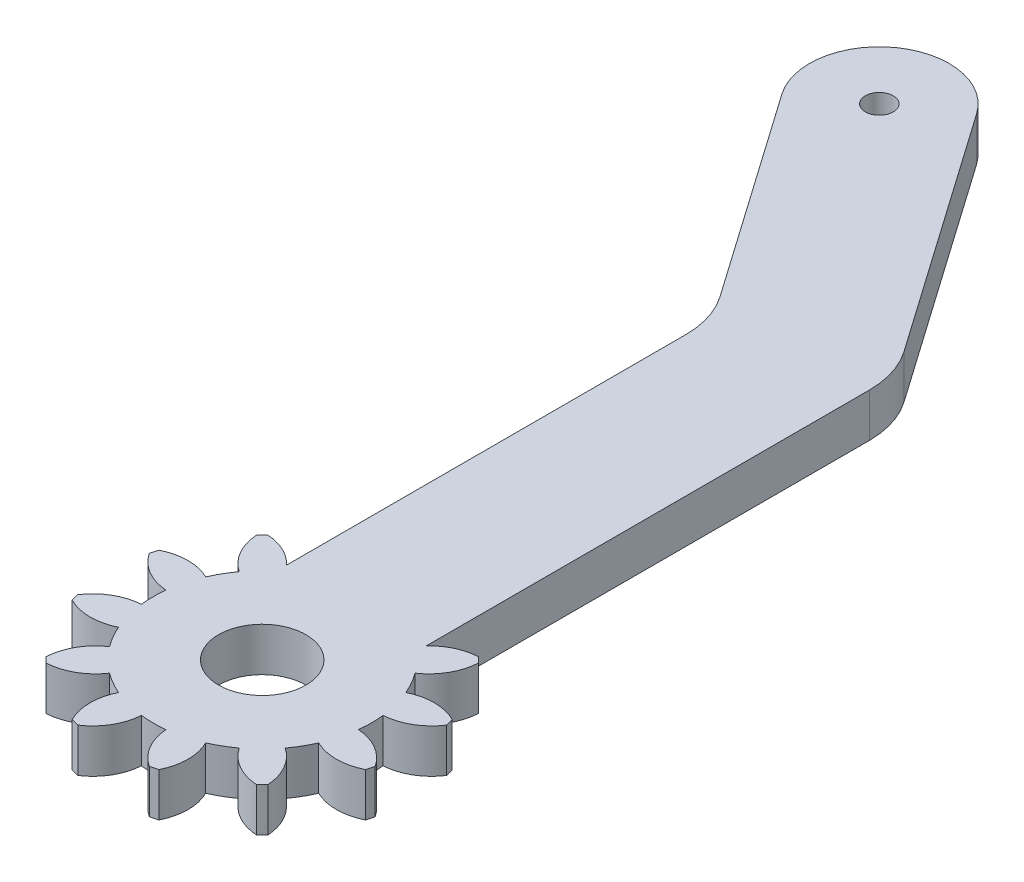
SolidWorks part; units mm, degrees
ref_plane "Front Plane" through (0, 0, 0) normal (0, 0, 1) x (1, 0, 0)
ref_plane "Top Plane" through (0, 0, 0) normal (0, 1, 0) x (1, 0, 0)
ref_plane "Right Plane" through (0, 0, 0) normal (1, 0, 0) x (0, 0, -1)
sketch "Sketch1" plane through (0, 0, 0) normal (0, 1, 0) x (1, 0, 0)
  line L1 (8, 9.6047) -> (8, 64.6702)
  line L2 (8, 96.9801) -> (-8, 96.9801) construction
  line L3 (-8, 96.9801) -> (-8, 59.6254) construction
  line L4 (0, 0) -> (0, 47.5503) construction
  line L5 (-8, 59.6254) -> (-30.9431, 92.3915)
  line L6 (-30.9431, 92.3915) -> (-17.8366, 101.5687)
  line L7 (-17.8366, 101.5687) -> (8, 64.6702)
  line L8 (-8, 59.6254) -> (-8, 9.6047)
  line L9 (8, 64.6702) -> (8, 96.9801) construction
  arc A0 (-8, 9.6047) -> (8, 9.6047) centre (0, 0) ccw
  point P1 (-24.3898, 96.9801)
  dimension "D1" = 25
  dimension "D2" = 16
  dimension "D3" = 100
  dimension "D4" = 16
  dimension "D5" = 145
  dimension "D6" = 40
extrude "Boss-Extrude1" add sketch "Sketch1" along normal blind 5
fillet "Fillet1" 2 edges at (-30.9431, 2.5, -92.3915) (-17.8366, 2.5, -101.5687) type full round first side face at (-19.4715, 2.5, -76.0084) second side face at (-4.9183, 2.5, -83.1194) middle face at (-24.3898, 2.5, -96.9801)
fillet "Fillet2" radius 10 2 edges at (8, 2.5, -64.6702) (-8, 2.5, -59.6254)
sketch "Sketch2" plane through (0, 5, 0) normal (0, 1, 0) x (1, 0, 0)
  circle A0 centre (-19.8012, 90.4269) radius 1.6
  dimension "D1" = 3.2
extrude "Cut-Extrude2" cut sketch "Sketch2" against normal through all contours A0
sketch "Sketch5" plane through (0, 5, 0) normal (0, 1, 0) x (1, 0, 0)
  arc A0 (-12.0517, -12.6888) -> (-7.1035, -9.5148) centre (-12.4017, -6.699) ccw
  arc A1 (-7.1035, -9.5148) -> (-4.6884, -10.9092) centre (0, 0) ccw
  arc A2 (-4.6884, -10.9092) -> (-4.963, -16.7815) centre (0.3993, -14.0897) ccw
  arc A3 (-4.963, -16.7815) -> (-4.0927, -17.0147) centre (0, 0) ccw
  arc A4 (-4.0927, -17.0147) -> (-1.3944, -11.7918) centre (-7.3907, -12.0024) ccw
  arc A5 (-1.3944, -11.7918) -> (1.3944, -11.7918) centre (0, 0) ccw
  arc A6 (1.3944, -11.7918) -> (4.0927, -17.0147) centre (7.3907, -12.0024) ccw
  arc A7 (4.0927, -17.0147) -> (4.963, -16.7815) centre (0, 0) ccw
  arc A8 (4.963, -16.7815) -> (4.6884, -10.9092) centre (-0.3993, -14.0897) ccw
  arc A9 (4.6884, -10.9092) -> (7.1035, -9.5148) centre (0, 0) ccw
  arc A10 (7.1035, -9.5148) -> (12.0517, -12.6888) centre (12.4017, -6.699) ccw
  arc A11 (12.0517, -12.6888) -> (12.6888, -12.0517) centre (0, 0) ccw
  arc A12 (12.6888, -12.0517) -> (9.5148, -7.1035) centre (6.699, -12.4017) ccw
  arc A13 (9.5148, -7.1035) -> (10.9092, -4.6884) centre (0, 0) ccw
  arc A14 (10.9092, -4.6884) -> (16.7815, -4.963) centre (14.0897, 0.3993) ccw
  arc A15 (16.7815, -4.963) -> (17.0147, -4.0927) centre (0, 0) ccw
  arc A16 (17.0147, -4.0927) -> (11.7918, -1.3944) centre (12.0024, -7.3907) ccw
  arc A17 (11.7918, -1.3944) -> (11.7918, 1.3944) centre (0, 0) ccw
  arc A18 (11.7918, 1.3944) -> (17.0147, 4.0927) centre (12.0024, 7.3907) ccw
  arc A19 (17.0147, 4.0927) -> (16.7815, 4.963) centre (0, 0) ccw
  arc A20 (16.7815, 4.963) -> (10.9092, 4.6884) centre (14.0897, -0.3993) ccw
  arc A21 (10.9092, 4.6884) -> (9.5148, 7.1035) centre (0, 0) ccw
  arc A22 (9.5148, 7.1035) -> (12.6888, 12.0517) centre (6.699, 12.4017) ccw
  arc A23 (12.6888, 12.0517) -> (12.0517, 12.6888) centre (0, 0) ccw
  arc A24 (12.0517, 12.6888) -> (7.1035, 9.5148) centre (12.4017, 6.699) ccw
  arc A25 (7.1035, 9.5148) -> (4.6884, 10.9092) centre (0, 0) ccw
  arc A26 (4.6884, 10.9092) -> (4.963, 16.7815) centre (-0.3993, 14.0897) ccw
  arc A27 (4.963, 16.7815) -> (4.0927, 17.0147) centre (0, 0) ccw
  arc A28 (4.0927, 17.0147) -> (1.3944, 11.7918) centre (7.3907, 12.0024) ccw
  arc A29 (1.3944, 11.7918) -> (-1.3944, 11.7918) centre (0, 0) ccw
  arc A30 (-1.3944, 11.7918) -> (-4.0927, 17.0147) centre (-7.3907, 12.0024) ccw
  arc A31 (-4.0927, 17.0147) -> (-4.963, 16.7815) centre (0, 0) ccw
  arc A32 (-4.963, 16.7815) -> (-4.6884, 10.9092) centre (0.3993, 14.0897) ccw
  arc A33 (-4.6884, 10.9092) -> (-7.1035, 9.5148) centre (0, 0) ccw
  arc A34 (-7.1035, 9.5148) -> (-12.0517, 12.6888) centre (-12.4017, 6.699) ccw
  arc A35 (-12.0517, 12.6888) -> (-12.6888, 12.0517) centre (0, 0) ccw
  arc A36 (-12.6888, 12.0517) -> (-9.5148, 7.1035) centre (-6.699, 12.4017) ccw
  arc A37 (-9.5148, 7.1035) -> (-10.9092, 4.6884) centre (0, 0) ccw
  arc A38 (-10.9092, 4.6884) -> (-16.7815, 4.963) centre (-14.0897, -0.3993) ccw
  arc A39 (-16.7815, 4.963) -> (-17.0147, 4.0927) centre (0, 0) ccw
  arc A40 (-17.0147, 4.0927) -> (-11.7918, 1.3944) centre (-12.0024, 7.3907) ccw
  arc A41 (-11.7918, 1.3944) -> (-11.7918, -1.3944) centre (0, 0) ccw
  arc A42 (-11.7918, -1.3944) -> (-17.0147, -4.0927) centre (-12.0024, -7.3907) ccw
  arc A43 (-17.0147, -4.0927) -> (-16.7815, -4.963) centre (0, 0) ccw
  arc A44 (-16.7815, -4.963) -> (-10.9092, -4.6884) centre (-14.0897, 0.3993) ccw
  arc A45 (-10.9092, -4.6884) -> (-9.5148, -7.1035) centre (0, 0) ccw
  arc A46 (-9.5148, -7.1035) -> (-12.6888, -12.0517) centre (-6.699, -12.4017) ccw
  arc A47 (-12.6888, -12.0517) -> (-12.0517, -12.6888) centre (0, 0) ccw
extrude "Boss-Extrude3" add sketch "Sketch5" against normal blind 5
sketch "Sketch6" plane through (0, 5, 0) normal (0, 1, 0) x (1, 0, 0)
  circle A0 centre (0, 0) radius 5
  dimension "D1" = 10
extrude "Cut-Extrude3" cut sketch "Sketch6" against normal through all
